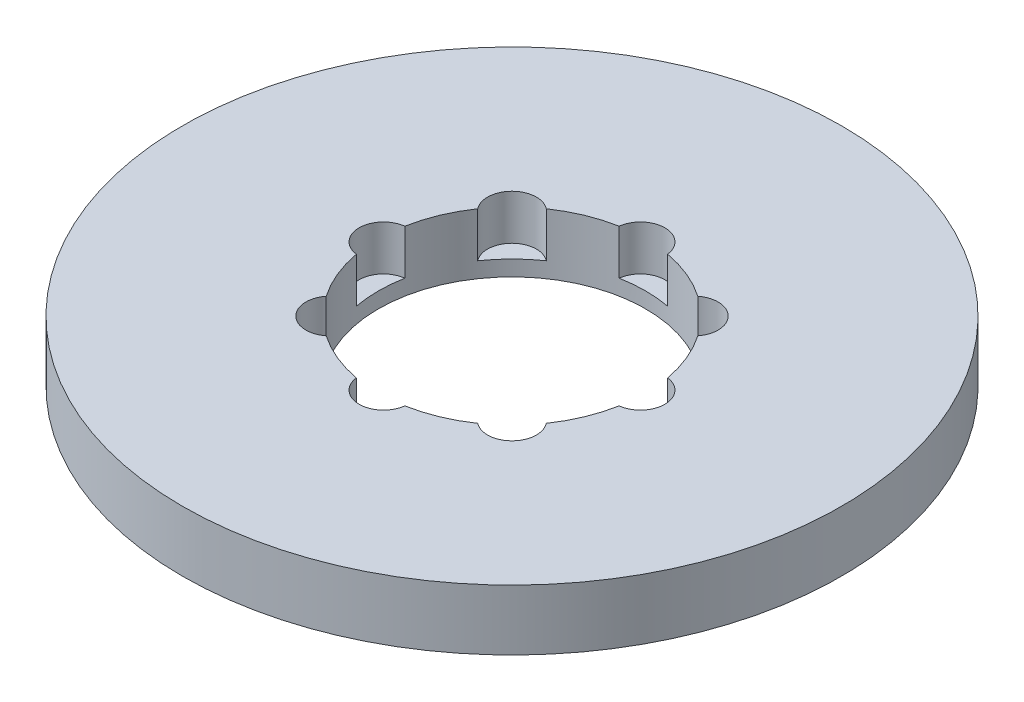
SolidWorks part; units mm, degrees
ref_plane "Front Plane" through (0, 0, 0) normal (0, 0, 1) x (1, 0, 0)
ref_plane "Top Plane" through (0, 0, 0) normal (0, 1, 0) x (1, 0, 0)
ref_plane "Right Plane" through (0, 0, 0) normal (1, 0, 0) x (0, 0, -1)
sketch "Sketch1" plane through (0, 0, 0) normal (0, 1, 0) x (1, 0, 0)
  circle A0 centre (0, 0) radius 92.5
  dimension "FLANGE_OD" = 185
extrude "Boss-Extrude1" add sketch "Sketch1" along normal blind 17
sketch "Sketch2" plane through (0, 0, 0) normal (0, 1, 0) x (1, 0, 0)
  circle A0 centre (0, 0) radius 37.5
  dimension "BORE_D" = 75
extrude "Cut-Extrude1" cut sketch "Sketch2" along normal through all
sketch "Sketch3" plane through (0, 17, 0) normal (0, 1, 0) x (1, 0, 0)
  circle A0 centre (0, 0) radius 36.0496 construction
  circle A1 centre (-36.0496, 0) radius 6.8561
  dimension "BOLT_D" = 13.7122
  dimension "BOLT_PCD" = 72.0991
extrude "Cut-Extrude2" cut sketch "Sketch3" against normal blind 12.6431
pattern_circular "CirPattern1" count 8 over 360 about axis through (0, 0, 0) along (0, 1, 0) of "Cut-Extrude2"
